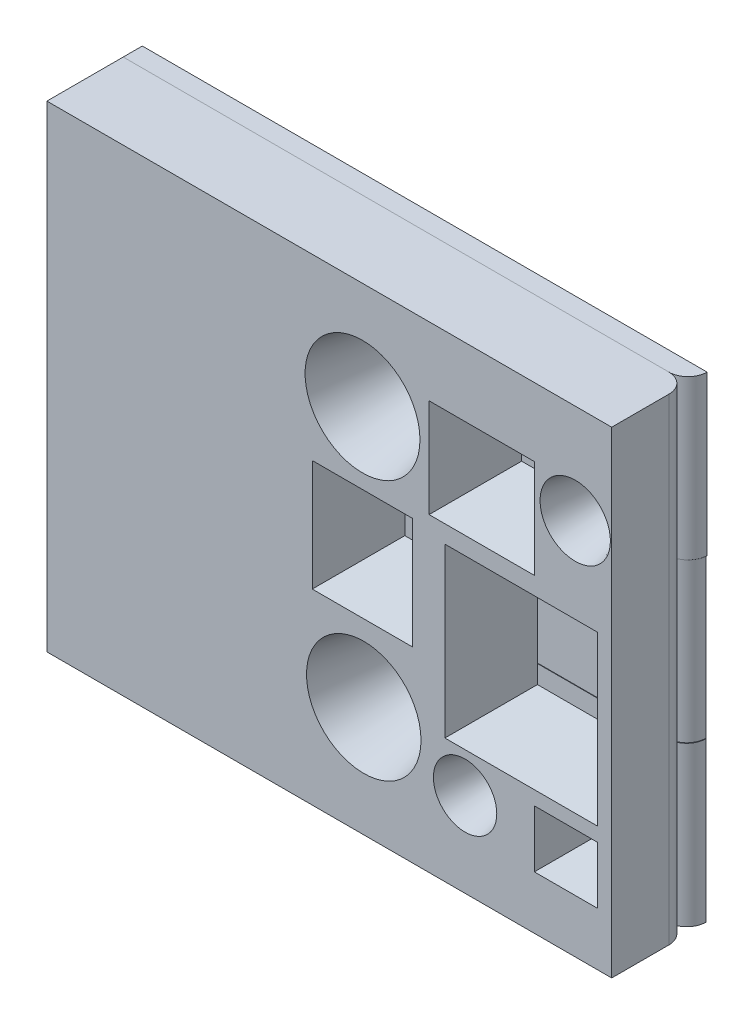
SolidWorks part; units mm, degrees
ref_plane "Front Plane" through (0, 0, 0) normal (0, 0, 1) x (1, 0, 0)
ref_plane "Top Plane" through (0, 0, 0) normal (0, 1, 0) x (1, 0, 0)
ref_plane "Right Plane" through (0, 0, 0) normal (1, 0, 0) x (0, 0, -1)
sketch "Sketch2" plane through (0, 0, 0) normal (0, 0, 1) x (1, 0, 0)
  line L1 (0, 0) -> (296, 0)
  line L2 (0, 0) -> (0, 250)
  line L3 (0, 250) -> (296, 250)
  line L4 (296, 0) -> (296, 250)
extrude "Boss-Extrude1" add sketch "Sketch2" along normal blind 40
sketch "Sketch4" plane through (0, 0, 0) normal (0, 0, -1) x (-1, 0, 0)
  line L0 (0, 250) -> (0, 0) construction
  line L1 (-296, 250) -> (0, 250)
  line L2 (-296, 250) -> (-296, 166.7)
  line L3 (-296, 166.7) -> (0, 166.7)
  line L4 (0, 250) -> (0, 166.7)
  line L5 (-295.3622, 83.2641) -> (0.6378, 83.2641)
  line L6 (-295.3622, 83.2641) -> (-295.3622, -0.0359)
  line L7 (-295.3622, -0.0359) -> (0.6378, -0.0359)
  line L8 (0.6378, 83.2641) -> (0.6378, -0.0359)
  line L9 (248.1269, 249.717) -> (544.1269, 249.717)
  line L10 (248.1269, 249.717) -> (248.1269, 166.417)
  line L11 (248.1269, 166.417) -> (544.1269, 166.417)
  line L12 (544.1269, 249.717) -> (544.1269, 166.417)
  line L13 (-295.3622, 166.8094) -> (0.6378, 166.8094)
  line L14 (-295.3622, 166.8094) -> (-295.3622, 83.5094)
  line L15 (-295.3622, 83.5094) -> (0.6378, 83.5094)
  line L16 (0.6378, 166.8094) -> (0.6378, 83.5094)
  line M13 (0, 0) -> (0, 250)
  line M14 (0, 250) -> (-296, 250)
  line M15 (-296, 250) -> (-296, 0)
  line M16 (-296, 0) -> (0, 0)
extrude "Boss-Extrude2" add sketch "Sketch4" along normal blind 10 separate body contours L14 L13 L4 L3 M14 M15 | L14 L15 L3 M13 | L5 L6 M16 M13 region at (148.0004, 208.4046, 0) region at (147.6811, 125.1047, 0) region at (147.6811, 41.6321, 0)
fillet "Fillet1" radius 10 1 edges at (296, 125, 0)
fillet "Fillet4" radius 10 1 edges at (296, 208.35, 0)
fillet "Fillet5" radius 10 1 edges at (295.3622, 125.1047, 0)
fillet "Fillet6" radius 10 1 edges at (295.3622, 41.6321, 0)
sketch "Sketch5" plane through (0, 0, 0) normal (-1, 0, 0) x (0, 0, 1)
  line L0 (0, 0) -> (0, 83.2641) construction
  line L1 (0, 83.2641) -> (-10, 83.2641) construction
  line L2 (-10, 83.2641) -> (-10, 0) construction
  line L3 (-10, 0) -> (0, 0) construction
  line L4 (0, 83.5094) -> (0, 166.7) construction
  line L5 (0, 166.7) -> (-10, 166.7) construction
  line L6 (-10, 166.7) -> (-10, 83.5094) construction
  line L7 (-10, 83.5094) -> (0, 83.5094) construction
  line L8 (0, 166.8094) -> (0, 250) construction
  line L9 (0, 250) -> (-10, 250) construction
  line L10 (-10, 250) -> (-10, 166.8094) construction
  line L11 (-10, 166.8094) -> (0, 166.8094) construction
  line L12 (0, 250) -> (0, 0) construction
  line L13 (0, 0) -> (40, 0) construction
  line L14 (40, 0) -> (40, 250) construction
  line L15 (40, 250) -> (0, 250) construction
  line L16 (0, 0) -> (0, 83.2641)
  line L17 (0, 83.2641) -> (-10, 83.2641)
  line L18 (-10, 83.2641) -> (-10, 0)
  line L19 (-10, 0) -> (0, 0)
  line L20 (0, 83.5094) -> (0, 166.7)
  line L21 (0, 166.7) -> (-10, 166.7)
  line L22 (-10, 166.7) -> (-10, 83.5094)
  line L23 (-10, 83.5094) -> (0, 83.5094)
  line L24 (0, 166.8094) -> (0, 250)
  line L25 (0, 250) -> (-10, 250)
  line L26 (-10, 250) -> (-10, 166.8094)
  line L27 (-10, 166.8094) -> (0, 166.8094)
  line L28 (0, 250) -> (0, 0)
  line L29 (0, 0) -> (40, 0)
  line L30 (40, 0) -> (40, 250)
  line L31 (40, 250) -> (0, 250)
sketch "Sketch6" plane through (0, 0, 40) normal (0, 0, 1) x (1, 0, 0)
  line L1 (295.3187, 225) -> (135.3187, 225)
  line L2 (295.3187, 225) -> (295.3187, 25)
  line L3 (295.3187, 25) -> (135.3187, 25)
  line L4 (135.3187, 225) -> (135.3187, 25)
  dimension "D1" = 200
  dimension "D2" = 160
sketch "Sketch8" plane through (0, 0, 40) normal (0, 0, 1) x (1, 0, 0)
  line L1 (139.0715, 156.4092) -> (191.6859, 156.4092)
  line L2 (139.0715, 156.4092) -> (139.0715, 98.055)
  line L3 (139.0715, 98.055) -> (191.6859, 98.055)
  line L4 (191.6859, 156.4092) -> (191.6859, 98.055)
  line L5 (208.5863, 153.2205) -> (288.624, 153.2205)
  line L6 (208.5863, 153.2205) -> (208.5863, 65.2109)
  line L7 (208.5863, 65.2109) -> (288.624, 65.2109)
  line L8 (288.624, 153.2205) -> (288.624, 65.2109)
  line L9 (200.2956, 214.1257) -> (255.461, 214.1257)
  line L10 (200.2956, 214.1257) -> (200.2956, 162.4679)
  line L11 (200.2956, 162.4679) -> (255.461, 162.4679)
  line L12 (255.461, 214.1257) -> (255.461, 162.4679)
  line L13 (255.461, 57.8767) -> (288.624, 57.8767)
  line L14 (255.461, 57.8767) -> (255.461, 27.9025)
  line L15 (255.461, 27.9025) -> (288.624, 27.9025)
  line L16 (288.624, 57.8767) -> (288.624, 27.9025)
  circle A0 centre (165.4164, 194.0365) radius 30.0977
  circle A1 centre (166.0666, 57.8767) radius 30
  circle A2 centre (276.8878, 197.9906) radius 18.431
  circle A3 centre (219.1613, 44.3861) radius 16.6022
extrude "Cut-Extrude1" cut sketch "Sketch8" against normal blind 45 draft 12 contours A0 | L2 L1 L4 L3 | A1 | L6 L5 L8 L7 | L10 L9 L12 L11 | A2 | L14 L13 L16 L15 | A3
